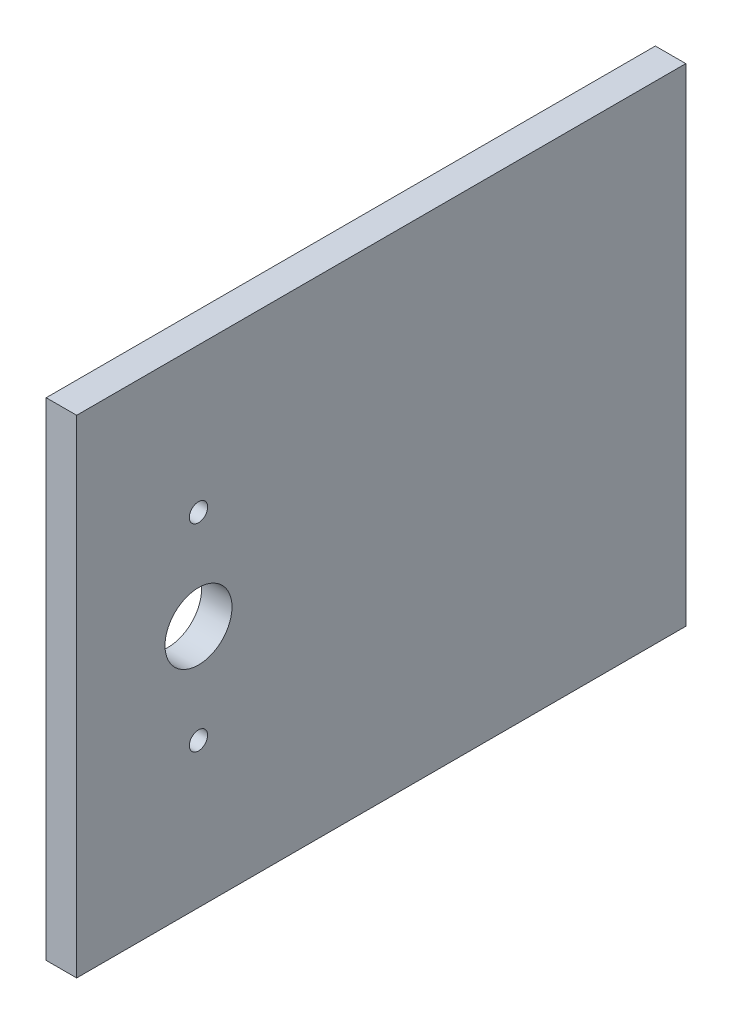
SolidWorks part; units mm, degrees
ref_plane "Front Plane" through (0, 0, 0) normal (1, 0, 0) x (0, 1, 0)
ref_plane "Top Plane" through (0, 0, 0) normal (0, 0, 1) x (0, 1, 0)
ref_plane "Right Plane" through (0, 0, 0) normal (0, 1, 0) x (-1, 0, 0)
sketch "Sketch1" plane through (0, 0, 0) normal (1, 0, 0) x (0, 1, 0)
  line L0 (0, 50) -> (0, -50) construction
  line L1 (-40, -50) -> (40, -50)
  line L2 (-40, -50) -> (-40, 50)
  line L3 (-40, 50) -> (40, 50)
  line L4 (40, -50) -> (40, 50)
  line L5 (-40, -50) -> (40, 50) construction
  line L6 (-40, 50) -> (40, -50) construction
  line L7 (-40, 30) -> (40, 30) construction
  circle A5 centre (0, 30) radius 5.5
  circle A6 centre (-16.22, 30) radius 1.5
  circle A7 centre (16.22, 30) radius 1.5
  point P0 (0, 0)
  dimension "D5" = 16.22
  dimension "D8" = 11
  dimension "D4" = 3
  dimension "D1" = 80
  dimension "D2" = 100
  dimension "D3" = 80
extrude "Boss-Extrude1" add sketch "Sketch1" along normal blind 5
